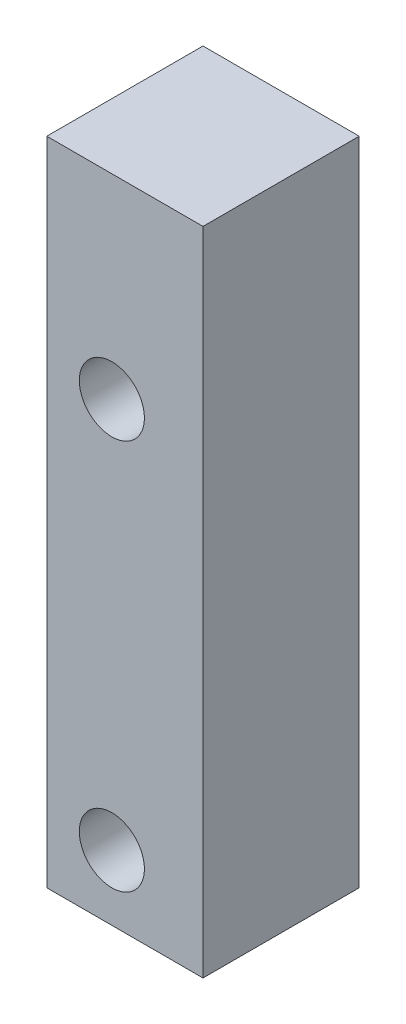
SolidWorks part; units mm, degrees
ref_plane "Front" through (0, 0, 0) normal (0, 0, 1) x (1, 0, 0)
ref_plane "Top" through (0, 0, 0) normal (0, 1, 0) x (1, 0, 0)
ref_plane "Right" through (0, 0, 0) normal (1, 0, 0) x (0, 0, -1)
sketch "Esquisse1" plane through (0, 0, 0) normal (0, 0, 1) x (1, 0, 0)
  line L1 (0, 0) -> (12, 0)
  line L2 (0, 0) -> (0, 50)
  line L3 (0, 50) -> (12, 50)
  line L4 (12, 0) -> (12, 50)
  dimension "D1" = 12
  dimension "D2" = 50
extrude "Boss.-Extru.1" add sketch "Esquisse1" along normal blind 12
sketch "Esquisse3" plane through (0, 0, 12) normal (0, 0, 1) x (1, 0, 0)
  line L0 (5, 50) -> (5, 0) construction
  line L2 (0, 0) -> (12, 0) construction
  line L3 (12, 50) -> (0, 50) construction
  line L4 (0, 50) -> (0, 0) construction
  circle A0 centre (5, 5) radius 2.5
  circle A1 centre (5, 35) radius 2.5
  point P2 (2.6314, 50)
  point P10 (0, 0)
  point P11 (0, 0)
  point P13 (3.0322, 0)
  dimension "D1" = 30
  dimension "D2" = 5
  dimension "D3" = 5
  dimension "D4" = 5
extrude "Enlèv. mat.-Extru.1" cut sketch "Esquisse3" against normal through all both and the other way through all
